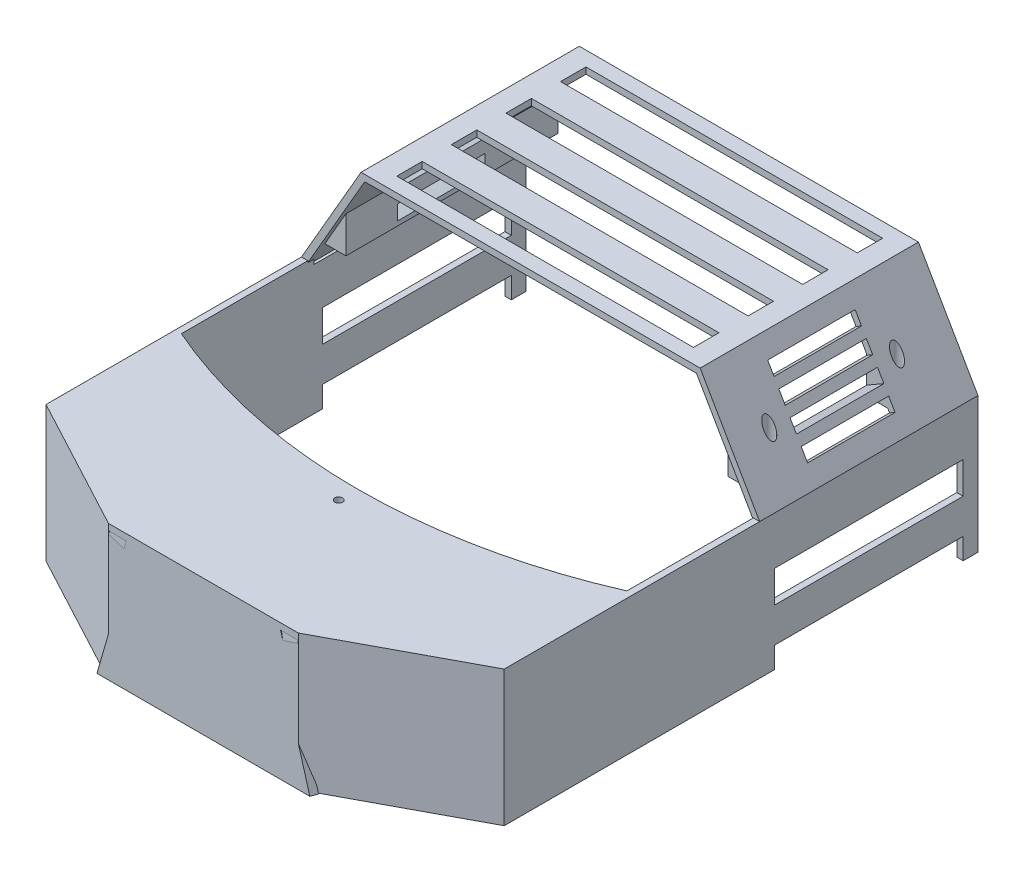
SolidWorks part; units mm, degrees
ref_plane "Alzado" through (0, 0, 0) normal (0, 0, 1) x (1, 0, 0)
ref_plane "Planta" through (0, 0, 0) normal (0, 1, 0) x (1, 0, 0)
ref_plane "Vista lateral" through (0, 0, 0) normal (1, 0, 0) x (0, 0, -1)
sketch "Croquis22" plane through (0, 0, 0) normal (0, 0, 1) x (1, 0, 0)
  line L0 (-54, 0) -> (54, 0)
  line L1 (0, 0) -> (0, 64) construction
  line L2 (54, 0) -> (35.5273, 64)
  line L3 (35.5273, 64) -> (-35.5273, 64)
  line L4 (-54, 0) -> (-35.5273, 64)
  point P4 (0, 0)
  dimension "D1" = 108
  dimension "D2" = 64
  dimension "D3" = 73.9
extrude "Saliente-Extruir15" add sketch "Croquis22" along normal blind 3
sketch "Croquis23" plane through (0, 64, 0) normal (0, 1, 0) x (1, 0, 0)
  line L0 (0, 0) -> (0, -59.7264) construction
  line L1 (35.5273, -3) -> (108.0682, 30.8264) construction
  line L2 (108.0682, 30.8264) -> (108.0682, 254.2864)
  line L3 (54, -3) -> (35.5273, -3) construction
  line L4 (108.0682, 254.2864) -> (105.0682, 254.2864)
  line L5 (105.0682, 32.7376) -> (34.8623, 0)
  line L6 (105.0682, 254.2864) -> (105.0682, 32.7376)
  line L7 (35.5273, 0) -> (-35.5273, 0) construction
  line L8 (44.7637, -3) -> (108.0682, 30.8264)
  line L9 (44.7637, -3) -> (34.8623, 0)
  line L10 (-44.7637, -3) -> (-108.0682, 30.8264)
  line L11 (-108.0682, 30.8264) -> (-108.0682, 254.2864)
  line L12 (-108.0682, 254.2864) -> (-105.0682, 254.2864)
  line L13 (-105.0682, 254.2864) -> (-105.0682, 32.7376)
  line L14 (-105.0682, 32.7376) -> (-34.8623, 0)
  line L15 (-44.7637, -3) -> (-34.8623, 0)
  dimension "D1" = 80.04
  dimension "D2" = 25
  dimension "D3" = 223.46
  dimension "D4" = 3
  dimension "D5" = 3
extrude "Saliente-Extruir16" add sketch "Croquis23" against normal up to surface (64 mm away) up to face at (0, 0, 1.5)
chamfer "Chaflán1" distance 8 angle 16 1 edges at (-40.1455, 48, 1.6008) first distance on face at (-41.6849, 53.3333, 2.0672)
chamfer "Chaflán2" distance 8 angle 16 1 edges at (40.1455, 48, 1.6008) first distance on face at (41.6849, 53.3333, 2.0672)
sketch "Croquis24" plane through (0, 64, 0) normal (0, 1, 0) x (1, 0, 0)
  line L0 (108.0682, 30.8264) -> (108.0682, 93.0064) construction
  line L1 (108.0682, 30.8264) -> (108.0682, 254.2864) construction
  line L2 (0, -3) -> (0, 69.74) construction
  line L3 (-108.0682, 30.8264) -> (-108.0682, 93.0064) construction
  line L4 (35.5273, -3) -> (-35.5273, -3) construction
  line L5 (-108.0682, 93.0064) -> (-108.0682, 30.8264)
  line L6 (-108.0682, 30.8264) -> (-44.7637, -3)
  line L7 (-44.7637, -3) -> (44.7637, -3)
  line L8 (44.7637, -3) -> (108.0682, 30.8264)
  line L9 (108.0682, 30.8264) -> (108.0682, 93.0064)
  arc A0 (-108.0682, 93.0064) -> (108.0682, 93.0064) centre (0, 332.3522) ccw
  dimension "D1" = 62.18
  dimension "D2" = 72.74
extrude "Saliente-Extruir17" add sketch "Croquis24" against normal blind 3
sketch "Croquis25" plane through (0, 0, -254.2864) normal (0, 0, -1) x (-1, 0, 0)
  line L1 (-108.0682, 64) -> (-79.9782, 112.6533)
  line L2 (105.0682, 64) -> (-105.0682, 64) construction
  line L3 (0, 0) -> (0, 89.2164) construction
  line L4 (108.0682, 64) -> (79.9782, 112.6533)
  line L5 (-79.9782, 112.6533) -> (79.9782, 112.6533)
  line L6 (-105.0682, 61) -> (105.0682, 61) construction
  line L7 (-78.2462, 109.6533) -> (78.2462, 109.6533)
  line L8 (-78.2462, 109.6533) -> (-105.0682, 63.1962)
  line L9 (-105.0682, 0) -> (-105.0682, 64) construction
  line L10 (78.2462, 109.6533) -> (105.0682, 63.1962)
  line L11 (105.0682, 0) -> (105.0682, 61) construction
  line L12 (-105.0682, 63.1962) -> (-108.0682, 64)
  line L13 (105.0682, 63.1962) -> (108.0682, 64)
  dimension "D1" = 60
  dimension "D2" = 56.18
  dimension "D3" = 51.6533
  dimension "D4" = 3
  dimension "D5" = 3
  dimension "D6" = 3
extrude "Saliente-Extruir18" add sketch "Croquis25" against normal blind 102.97
sketch "Croquis28" plane through (0, 61, 0) normal (0, -1, 0) x (1, 0, 0)
  circle A0 centre (-0.0018, -60.825) radius 1.825
  dimension "D1" = 3.65
extrude "Cortar-Extruir6" cut sketch "Croquis28" against normal through all
sketch "Croquis29" plane through (0, 0, -254.2864) normal (0, 0, -1) x (-1, 0, 0)
  line L0 (-105.0682, 61) -> (-90.0682, 61)
  line L1 (-105.0682, 61) -> (105.0682, 61) construction
  line L2 (-90.0682, 61) -> (-90.0682, 89.1769)
  line L3 (-105.0682, 63.1962) -> (-78.2462, 109.6533) construction
  line L4 (-105.0682, 61) -> (-105.0682, 63.1962)
  line L5 (-105.0682, 63.1962) -> (-90.0682, 89.1769)
  line L6 (0, 0) -> (0, 112.6533) construction
  line L7 (34.8623, 0) -> (-34.8623, 0) construction
  line L8 (79.9782, 112.6533) -> (-79.9782, 112.6533) construction
  line L9 (105.0682, 61) -> (105.0682, 63.1962)
  line L10 (105.0682, 61) -> (90.0682, 61)
  line L11 (90.0682, 61) -> (90.0682, 89.1769)
  line L12 (105.0682, 63.1962) -> (90.0682, 89.1769)
  dimension "D1" = 15
extrude "Saliente-Extruir19" add sketch "Croquis29" against normal blind 100
sketch "Croquis30" plane through (0, 61, 0) normal (0, -1, 0) x (1, 0, 0)
  line L0 (0, 3) -> (0, -304.7479) construction
  line L1 (-54, 3) -> (54, 3) construction
  circle A0 centre (94.8577, -169.0525) radius 1.65
  circle A1 centre (94.8577, -229.2969) radius 1.65
  circle A2 centre (-94.8577, -229.2969) radius 1.65
  circle A3 centre (-94.8577, -169.0525) radius 1.65
  dimension "D1" = 3.3
  dimension "D2" = 3.3
extrude "Cortar-Extruir7" cut sketch "Croquis30" against normal through all
sketch "Croquis31" plane through (0, 61, 0) normal (0, -1, 0) x (1, 0, 0)
  line L0 (-0.0018, -264.9998) -> (0, 3) construction
  line L1 (81.9982, -264.9998) -> (-82.0018, -264.9998) construction
  line L2 (-54, 3) -> (54, 3) construction
  circle A0 centre (94.8577, -169.0525) radius 3.5
  circle A1 centre (94.8577, -229.2969) radius 2.75
  circle A2 centre (-94.8608, -229.2956) radius 2.75
  circle A3 centre (-94.86, -169.0512) radius 3.5
  dimension "D1" = 7
  dimension "D2" = 5.5
sketch "Croquis32" plane through (0, 0, -254.2864) normal (0, 0, -1) x (-1, 0, 0)
  line L0 (-105.0682, 0) -> (-105.0682, 61) construction
  line L1 (-105.0682, 47.75) -> (-90.0682, 47.75)
  line L2 (-105.0682, 47.75) -> (-105.0682, 39.75)
  line L3 (-105.0682, 39.75) -> (-90.0682, 39.75)
  line L4 (-90.0682, 47.75) -> (-90.0682, 39.75)
  line L5 (-90.0682, 61) -> (-90.0682, 89.1769) construction
  line L6 (0, 112.6533) -> (0, 64) construction
  line L7 (79.9782, 112.6533) -> (-79.9782, 112.6533) construction
  line L8 (105.0682, 64) -> (-105.0682, 64) construction
  line L9 (-99.9982, 49) -> (-94.6236, 49) construction
  line L10 (105.0682, 39.75) -> (90.0682, 39.75)
  line L11 (90.0682, 47.75) -> (90.0682, 39.75)
  line L12 (105.0682, 47.75) -> (90.0682, 47.75)
  line L13 (105.0682, 47.75) -> (105.0682, 39.75)
  dimension "D1" = 1.25
  dimension "D2" = 8
sketch "Croquis33" plane through (0, 0, -254.2864) normal (0, 0, -1) x (-1, 0, 0)
  line L0 (0, 122.8302) -> (0, 0) construction
  line L1 (-90.0682, 89.1769) -> (-108.0682, 58) construction
  line L2 (-79.9782, 112.6533) -> (-108.0682, 64) construction
  line L3 (-90.0682, 61) -> (-90.0682, 89.1769) construction
  line L4 (-108.0682, 0) -> (-108.0682, 64) construction
  line L5 (-90.0682, 61) -> (-90.0682, 72)
  line L6 (-90.0682, 72) -> (-99.9853, 72)
  line L7 (-99.9853, 72) -> (-106.3362, 61)
  line L8 (-106.3362, 61) -> (-90.0682, 61)
  line L9 (99.9853, 72) -> (106.3362, 61)
  line L10 (90.0682, 72) -> (99.9853, 72)
  line L11 (90.0682, 61) -> (90.0682, 72)
  line L12 (106.3362, 61) -> (90.0682, 61)
  dimension "D1" = 3
  dimension "D2" = 11
extrude "Cortar-Extruir9" cut sketch "Croquis33" against normal up to surface (100 mm away) up to face at (97.5682, 68.5933, -154.2864)
sketch "Croquis34" plane through (0, 72, 0) normal (0, -1, 0) x (1, 0, 0)
  line L0 (0, 3) -> (-0.0018, -253.9748) construction
  line L1 (41.8732, -253.9748) -> (-41.8768, -253.9748) construction
  circle A0 centre (94.8577, -169.0525) radius 2.5
  circle A1 centre (94.8577, -229.2969) radius 2.5
  circle A2 centre (-94.8601, -169.0512) radius 2.5
  circle A3 centre (-94.8609, -229.2956) radius 2.5
  dimension "D1" = 5
  dimension "D2" = 5
extrude "Cortar-Extruir10" cut sketch "Croquis34" along normal blind 35 from surface starting at face at (0, 112.6533, -202.8014)
sketch "Croquis35" plane through (108.764, 62.7949, 0) normal (0.866, 0.5, 0) x (0, 0, -1)
  line L0 (178.5525, 29.4815) -> (178.5525, 50.5715) construction
  line L1 (178.5525, 50.5715) -> (219.7969, 50.5715) construction
  line L2 (178.5525, 50.5715) -> (178.5525, 8.3915) construction
  line L3 (178.5525, 8.3915) -> (219.7969, 8.3915) construction
  line L4 (219.7969, 50.5715) -> (219.7969, 8.3915) construction
  line L5 (178.5525, 29.4815) -> (219.7969, 29.4815) construction
  line L6 (178.5525, 40.0265) -> (219.7969, 40.0265) construction
  line L7 (178.5525, 40.0265) -> (178.5525, 50.5715) construction
  line L8 (219.7969, 50.5715) -> (219.7969, 40.0265) construction
  line L9 (199.1747, 50.5715) -> (199.1747, 40.0265) construction
  line L10 (199.1747, 45.299) -> (178.5525, 45.299) construction
  line L11 (178.5525, 37.754) -> (219.7969, 37.754)
  line L12 (178.5525, 48.299) -> (219.7969, 48.299)
  line L13 (178.5525, 48.299) -> (178.5525, 42.299)
  line L14 (178.5525, 42.299) -> (219.7969, 42.299)
  line L15 (219.7969, 48.299) -> (219.7969, 42.299)
  line L16 (219.7969, 31.754) -> (219.7969, 37.754)
  line L17 (178.5525, 31.754) -> (219.7969, 31.754)
  line L18 (178.5525, 31.754) -> (178.5525, 37.754)
  line L19 (178.5525, 27.209) -> (178.5525, 21.209)
  line L20 (178.5525, 27.209) -> (219.7969, 27.209)
  line L21 (219.7969, 27.209) -> (219.7969, 21.209)
  line L22 (178.5525, 21.209) -> (219.7969, 21.209)
  line L23 (178.5525, 16.664) -> (219.7969, 16.664)
  line L24 (219.7969, 10.664) -> (219.7969, 16.664)
  line L25 (178.5525, 10.664) -> (219.7969, 10.664)
  line L26 (178.5525, 10.664) -> (178.5525, 16.664)
  point P18 (178.5525, 45.299)
  dimension "D1" = 3
extrude "Cortar-Extruir11" cut sketch "Croquis35" against normal blind 17
sketch "Croquis36" plane through (-108.764, 62.7949, 0) normal (-0.866, 0.5, 0) x (0, 0, 1)
  line L0 (-254.2864, 1.3915) -> (-254.2864, 57.5715) construction
  line L1 (-219.7956, 50.5715) -> (-178.5512, 50.5715) construction
  line L2 (-219.7956, 50.5715) -> (-219.7956, 8.3915) construction
  line L3 (-219.7956, 8.3915) -> (-178.5512, 8.3915) construction
  line L4 (-178.5512, 50.5715) -> (-178.5512, 8.3915) construction
  line L5 (-226.7956, 27.8061) -> (-171.5512, 27.8078) construction
  line L6 (-151.3164, 57.5715) -> (-254.2864, 57.5715) construction
  line L7 (-219.7956, 27.8063) -> (-219.7956, 50.5715) construction
  line L8 (-199.1734, 27.8069) -> (-199.1734, 50.5715) construction
  line L9 (-199.1734, 39.1892) -> (-219.7956, 39.1892) construction
  line L10 (-199.1734, 39.1892) -> (-199.1734, 50.5715) construction
  line L11 (-199.1734, 39.1892) -> (-191.157, 39.1892) construction
  line L12 (-191.157, 39.1892) -> (-191.157, 50.5715) construction
  line L13 (-191.157, 44.8804) -> (-219.7956, 44.8804) construction
  line L14 (-219.7956, 30.4981) -> (-178.5512, 30.4981)
  line L15 (-219.7956, 41.8804) -> (-178.5512, 41.8804)
  line L16 (-219.7956, 41.8804) -> (-219.7956, 47.8804)
  line L17 (-219.7956, 47.8804) -> (-178.5512, 47.8804)
  line L18 (-178.5512, 41.8804) -> (-178.5512, 47.8804)
  line L19 (-178.5512, 36.4981) -> (-178.5512, 30.4981)
  line L20 (-219.7956, 36.4981) -> (-178.5512, 36.4981)
  line L21 (-219.7956, 36.4981) -> (-219.7956, 30.4981)
  line L22 (-219.7951, 19.1145) -> (-219.7954, 25.1145)
  line L23 (-219.7951, 19.1145) -> (-178.5506, 19.117)
  line L24 (-178.5506, 19.117) -> (-178.551, 25.117)
  line L25 (-219.7954, 25.1145) -> (-178.551, 25.117)
  line L26 (-219.7944, 7.7322) -> (-178.55, 7.7347)
  line L27 (-178.5503, 13.7347) -> (-178.55, 7.7347)
  line L28 (-219.7947, 13.7322) -> (-178.5503, 13.7347)
  line L29 (-219.7947, 13.7322) -> (-219.7944, 7.7322)
  point P6 (-254.2864, 29.4815)
  point P7 (-219.7956, 29.4815)
  point P12 (-199.1734, 27.8069)
  point P13 (-199.1734, 50.5715)
  point P29 (-219.7956, 44.8804)
  dimension "D1" = 7
  dimension "D2" = 7
  dimension "D3" = 8.0164
  dimension "D4" = 6
extrude "Cortar-Extruir12" cut sketch "Croquis36" against normal blind 17
sketch "Croquis37" plane through (0, 112.6533, 0) normal (0, 1, 0) x (1, 0, 0)
  line L0 (0, 254.2864) -> (0, 151.3164) construction
  line L1 (-39.9891, 202.8014) -> (-39.9891, 254.2864) construction
  line L2 (-39.9891, 241.4151) -> (-79.9782, 241.4151) construction
  line L3 (-79.9782, 151.3164) -> (79.9782, 151.3164) construction
  line L4 (-79.9782, 254.2864) -> (79.9782, 254.2864) construction
  line L5 (-79.9782, 202.8014) -> (0, 202.8014) construction
  line L6 (-79.9782, 151.3164) -> (-79.9782, 254.2864) construction
  line L7 (-39.9891, 228.5439) -> (-79.9782, 228.5439) construction
  line L8 (-69.9782, 247.4151) -> (69.9782, 247.4151)
  line L9 (-69.9782, 247.4151) -> (-69.9782, 235.4151)
  line L10 (-69.9782, 235.4151) -> (69.9782, 235.4151)
  line L11 (69.9782, 247.4151) -> (69.9782, 235.4151)
  line L12 (-79.9782, 228.5439) -> (-79.9782, 254.2864) construction
  line L13 (-69.9782, 221.6726) -> (69.9782, 221.6726)
  line L14 (69.9782, 209.6726) -> (69.9782, 221.6726)
  line L15 (-69.9782, 209.6726) -> (69.9782, 209.6726)
  line L16 (-69.9782, 209.6726) -> (-69.9782, 221.6726)
  line L17 (-69.9782, 195.9301) -> (-69.9782, 183.9301)
  line L18 (-69.9782, 195.9301) -> (69.9782, 195.9301)
  line L19 (69.9782, 195.9301) -> (69.9782, 183.9301)
  line L20 (-69.9782, 183.9301) -> (69.9782, 183.9301)
  line L21 (-69.9782, 170.1876) -> (69.9782, 170.1876)
  line L22 (69.9782, 158.1876) -> (69.9782, 170.1876)
  line L23 (-69.9782, 158.1876) -> (69.9782, 158.1876)
  line L24 (-69.9782, 158.1876) -> (-69.9782, 170.1876)
  point P18 (-69.9782, 241.4151)
  point P19 (0, 247.4151)
  point P22 (-79.9782, 241.4151)
  dimension "D1" = 10
  dimension "D2" = 12
extrude "Cortar-Extruir13" cut sketch "Croquis37" against normal up to surface (3 mm away) up to face at (0, 109.6533, -202.8014)
sketch "Croquis39" plane through (-108.0682, 0, 0) normal (-1, 0, 0) x (0, 0, 1)
  line L0 (-254.2864, 26.3778) -> (-247.2864, 26.3778) construction
  line L1 (-254.2864, 0) -> (-254.2864, 64) construction
  line L2 (-30.8264, 0) -> (-254.2864, 0) construction
  line L3 (-151.3164, 64) -> (-151.3164, 26.3778) construction
  line L4 (-247.2864, 26.3778) -> (-158.3164, 26.3778)
  line L5 (-247.2864, 26.3778) -> (-247.2864, 41.3778)
  line L6 (-247.2864, 41.3778) -> (-158.3164, 41.3778)
  line L7 (-158.3164, 26.3778) -> (-158.3164, 41.3778)
  line L8 (-151.3164, 26.3778) -> (-158.3164, 26.3778) construction
  line L9 (-247.2864, 26.3778) -> (-247.2864, 0) construction
  line L11 (-247.2864, 0) -> (-158.3164, 0)
  line L12 (-247.2864, 0) -> (-247.2864, 10)
  line L13 (-247.2864, 10) -> (-158.3164, 10)
  line L14 (-158.3164, 0) -> (-158.3164, 10)
  dimension "D1" = 7
  dimension "D2" = 26.3778
  dimension "D3" = 7
  dimension "D4" = 15
  dimension "D5" = 10
extrude "Cortar-Extruir14" cut sketch "Croquis39" against normal through all
chamfer "Chaflán4" distance 10 angle 20 2 edges at (49.3818, 16, 3) (-49.3818, 16, 3) first distance on face at (50.7854, 11.1371, 1.5) first distance on face at (-50.7854, 11.1371, 1.5)
ref_plane "Plano1" through (-108.0682, 0, -158.3164) normal (0, 0, -1) x (-1, 0, 0)
